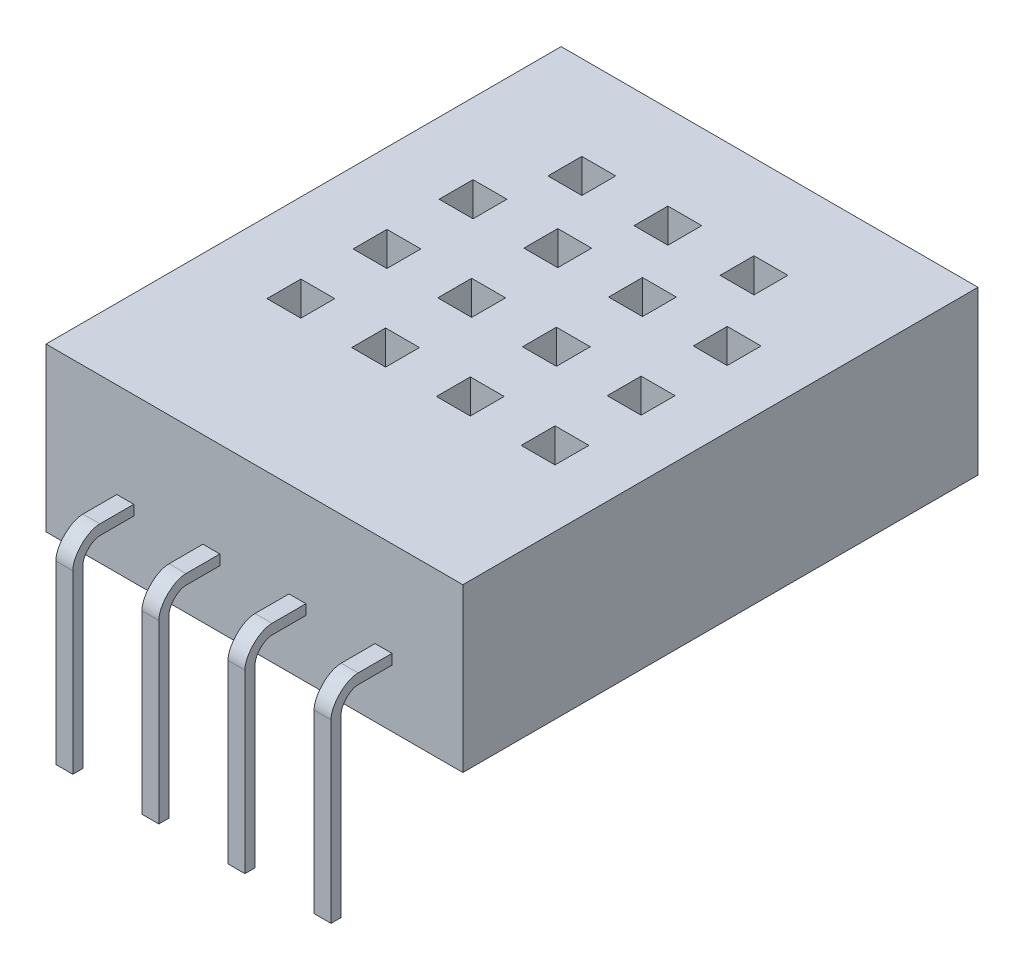
SolidWorks part; units mm, degrees
ref_plane "Front" through (0, 0, 0) normal (0, 0, 1) x (1, 0, 0)
ref_plane "Top" through (0, 0, 0) normal (0, 1, 0) x (1, 0, 0)
ref_plane "Right" through (0, 0, 0) normal (1, 0, 0) x (0, 0, -1)
sketch "Эскиз1" plane through (0, 0, 0) normal (0, 1, 0) x (1, 0, 0)
  line L1 (-6.15, -7.6) -> (6.15, -7.6)
  line L2 (-6.15, -7.6) -> (-6.15, 7.6)
  line L3 (-6.15, 7.6) -> (6.15, 7.6)
  line L4 (6.15, -7.6) -> (6.15, 7.6)
  line L5 (-6.15, -7.6) -> (6.15, 7.6) construction
  line L6 (-6.15, 7.6) -> (6.15, -7.6) construction
  point P0 (0, 0)
  dimension "D1" = 12.3
  dimension "D2" = 15.2
extrude "Бобышка-Вытянуть1" add sketch "Эскиз1" along normal blind 4.8
sketch "Эскиз2" plane through (0, 0, 7.6) normal (0, 0, 1) x (1, 0, 0)
  line L0 (-6.15, 0) -> (6.15, 0) construction
  line L1 (3.56, 1.7) -> (4.06, 1.7)
  line L2 (3.56, 1.7) -> (3.56, 2)
  line L3 (3.56, 2) -> (4.06, 2)
  line L4 (4.06, 1.7) -> (4.06, 2)
  line L5 (3.56, 1.7) -> (4.06, 2) construction
  line L6 (3.56, 2) -> (4.06, 1.7) construction
  point P0 (3.81, 1.85)
  dimension "D1" = 1.7
  dimension "D2" = 0.5
  dimension "D3" = 0.3
  dimension "D4" = 3.81
extrude "Бобышка-Вытянуть2" add sketch "Эскиз2" along normal blind 1 separate body
sketch "Эскиз5" plane through (0, 0, 0) normal (0, 1, 0) x (1, 0, 0)
  line L1 (4.06, -9.1) -> (3.56, -9.1)
  line L2 (4.06, -9.1) -> (4.06, -9.4)
  line L3 (4.06, -9.4) -> (3.56, -9.4)
  line L4 (3.56, -9.1) -> (3.56, -9.4)
  point P4 (0, 0)
  dimension "D1" = 0.3
  dimension "D2" = 0.5
extrude "Бобышка-Вытянуть3" add sketch "Эскиз5" along normal offset from surface 0.5 and the other way blind 4 separate body up to face at (3.81, 1.7, 8.1)
loft "По сечениям1" add section face at (3.81, 1.85, 8.6) section face at (3.81, 1.2, 9.25) start constraint normal to profile start tangent length 1 end constraint normal to profile end tangent length 1 connector at (3.56, 1.7, 8.6) connector at (3.56, 1.2, 9.1)
pattern_linear "Линейный массив1" count 4 spacing 2.54 along (-1, 0, 0) of bodies 111 102
sketch "Эскиз3" plane through (0, 4.8, 0) normal (0, 1, 0) x (1, 0, 0)
  line L0 (6.15, 7.6) -> (-6.15, 7.6) construction
  line L1 (-0.5, 5.1) -> (0.5, 5.1)
  line L2 (-0.5, 5.1) -> (-0.5, 4.1)
  line L3 (-0.5, 4.1) -> (0.5, 4.1)
  line L4 (0.5, 5.1) -> (0.5, 4.1)
  line L5 (-0.5, 5.1) -> (0.5, 4.1) construction
  line L6 (-0.5, 4.1) -> (0.5, 5.1) construction
  point P0 (0, 4.6)
  dimension "D1" = 2.5
  dimension "D2" = 1
extrude "Вырез-Вытянуть1" cut sketch "Эскиз3" against normal blind 2
pattern_linear "Линейный массив2" count 2 spacing 2.54 along (1, 0, 0) count 2 spacing 2.54 along (-1, 0, 0) of "Вырез-Вытянуть1"
sketch "Эскиз4" plane through (0, 4.8, 0) normal (0, 1, 0) x (1, 0, 0)
  line L0 (6.15, -7.6) -> (6.15, 7.6) construction
  line L1 (3.45, 2.9) -> (4.45, 2.9)
  line L2 (3.45, 2.9) -> (3.45, 1.9)
  line L3 (3.45, 1.9) -> (4.45, 1.9)
  line L4 (4.45, 2.9) -> (4.45, 1.9)
  line L5 (3.45, 2.9) -> (4.45, 1.9) construction
  line L6 (3.45, 1.9) -> (4.45, 2.9) construction
  line L7 (6.15, 7.6) -> (-6.15, 7.6) construction
  point P0 (3.95, 2.4)
  dimension "D1" = 1.7
  dimension "D2" = 1
  dimension "D3" = 4.7
extrude "Вырез-Вытянуть2" cut sketch "Эскиз4" against normal blind 2
pattern_linear "Линейный массив3" count 4 spacing 2.5 along (-1, 0, 0) count 3 spacing 2.54 along (0, 0, 1) of "Вырез-Вытянуть2"
